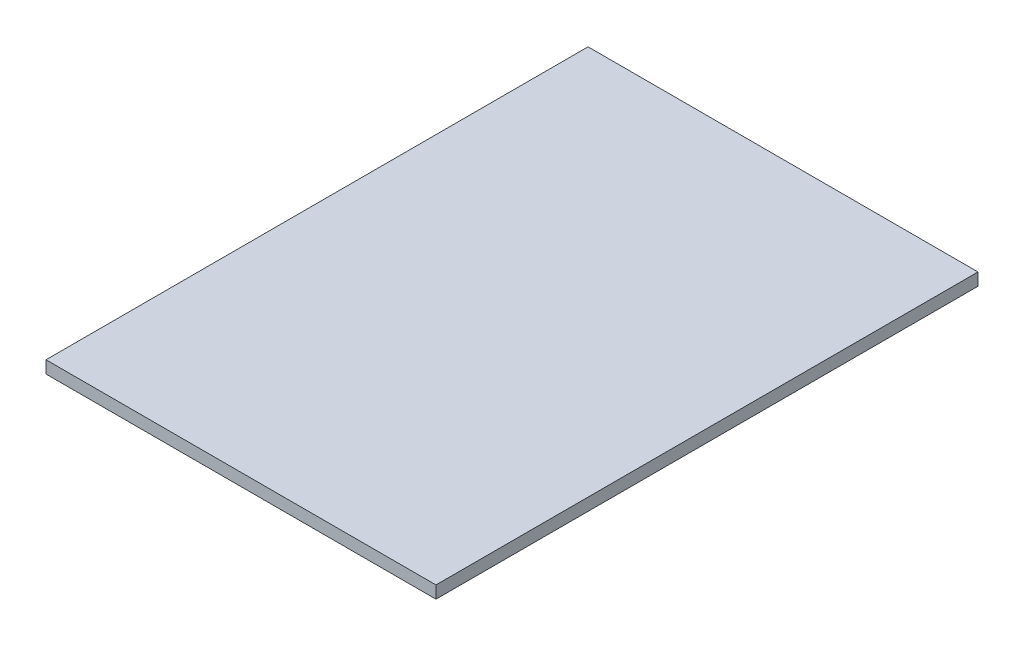
SolidWorks part; units mm, degrees
ref_plane "Front Plane" through (0, 0, 0) normal (0, 0, 1) x (1, 0, 0)
ref_plane "Top Plane" through (0, 0, 0) normal (0, 1, 0) x (1, 0, 0)
ref_plane "Right Plane" through (0, 0, 0) normal (1, 0, 0) x (0, 0, -1)
sketch "Sketch1" plane through (0, 0, 0) normal (0, 0, 1) x (1, 0, 0)
  line L1 (-50, 70.1122) -> (50, 70.1122)
  line L2 (-50, 70.1122) -> (-50, 73.2872)
  line L3 (-50, 73.2872) -> (50, 73.2872)
  line L4 (50, 70.1122) -> (50, 73.2872)
  point P0 (-88.3432, 73.1449)
  dimension "D1" = 3.175
  dimension "D2" = 100
extrude "Boss-Extrude1" add sketch "Sketch1" against normal blind 139
